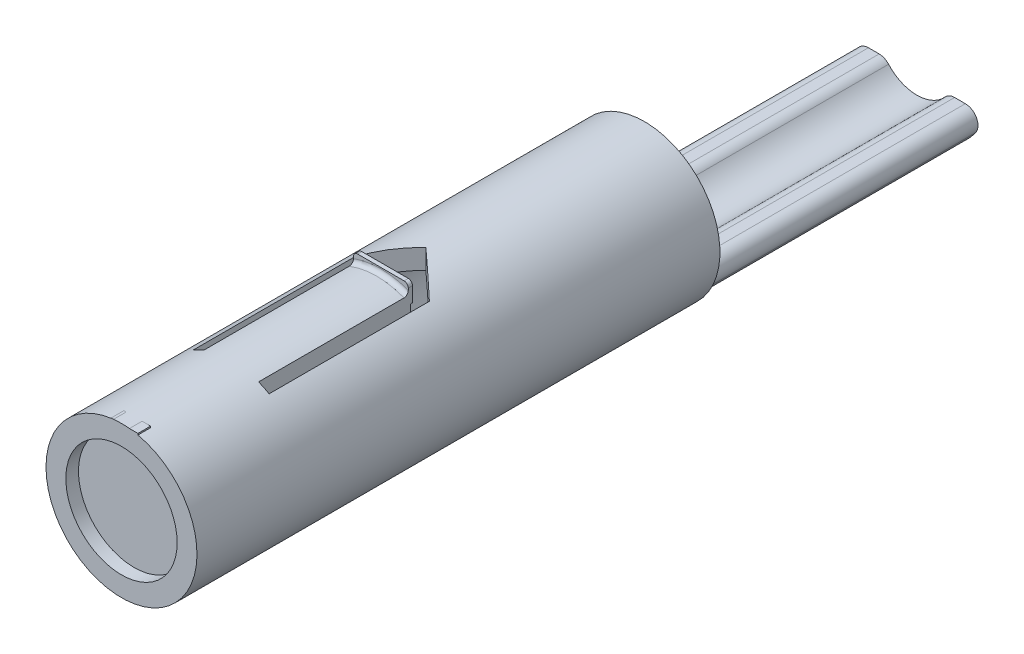
SolidWorks part; units mm, degrees
ref_plane "Front Plane" through (0, 0, 0) normal (0, 0, 1) x (1, 0, 0)
ref_plane "Top Plane" through (0, 0, 0) normal (0, 1, 0) x (1, 0, 0)
ref_plane "Right Plane" through (0, 0, 0) normal (1, 0, 0) x (0, 0, -1)
sketch "Sketch1" plane through (0, 0, 0) normal (0, 0, 1) x (1, 0, 0)
  circle A0 centre (0, 0) radius 8.95
  circle A1 centre (0, 0) radius 6.6
extrude "Boss-Extrude1" add sketch "Sketch1" along normal blind 62
sketch "Sketch2" plane through (0, 0, 62) normal (0, 0, 1) x (1, 0, 0)
  circle A0 centre (0, 0) radius 6.6
extrude "Boss-Extrude2" add sketch "Sketch2" against normal blind 7
sketch "Sketch4" plane through (0, 0, 62) normal (0, 0, 1) x (1, 0, 0)
  circle A0 centre (0, 0) radius 6.6
extrude "Cut-Extrude2" cut sketch "Sketch4" against normal blind 1.5
sketch "Sketch5" plane through (0, 0, 0) normal (0, 0, -1) x (-1, 0, 0)
  circle A0 centre (0, 0) radius 8.95
extrude "Boss-Extrude4" add sketch "Sketch5" against normal blind 10
sketch "Sketch6" plane through (0, 0, 0) normal (0, 0, -1) x (-1, 0, 0)
  circle A0 centre (0, 0) radius 9.0755
extrude "Boss-Extrude5" add sketch "Sketch6" along normal blind 32.3
sketch "Sketch7" plane through (0, 0, -32.3) normal (0, 0, -1) x (-1, 0, 0)
  line L1 (-5.8318, 9.3631) -> (5.9783, 9.3631)
  line L2 (-5.8318, 9.3631) -> (-5.8318, 2.7108)
  line L3 (-5.8318, 2.7108) -> (5.9783, 2.7108)
  line L4 (5.9783, 9.3631) -> (5.9783, 2.7108)
extrude "Cut-Extrude3" cut sketch "Sketch7" against normal blind 32.3
sketch "Sketch9" plane through (0, 0, -32.3) normal (0, 0, -1) x (-1, 0, 0)
  line L1 (-7.75, -9.08) -> (7.75, -9.08)
  line L2 (-7.75, -9.08) -> (-7.75, -0.98)
  line L3 (-7.75, -0.98) -> (7.75, -0.98)
  line L4 (7.75, -9.08) -> (7.75, -0.98)
  line L5 (-14.7241, -0.98) -> (14.7072, -0.98)
  line L6 (-14.7241, -0.98) -> (-14.7241, 9.3882)
  line L7 (-14.7241, 9.3882) -> (14.7072, 9.3882)
  line L8 (14.7072, -0.98) -> (14.7072, 9.3882)
  circle A0 centre (0, 0) radius 4.5
  arc A1 (-5.8318, 6.9537) -> (5.9783, 6.8282) centre (0, 0) ccw construction
  circle A2 centre (0, 0) radius 9.0755
  line M1 (-5.8318, 2.7108) -> (-5.8318, 6.9537)
  arc M2 (-5.8318, 6.9537) -> (5.9783, 6.8282) centre (0, 0) ccw
  line M3 (5.9783, 6.8282) -> (5.9783, 2.7108)
  line M4 (5.9783, 2.7108) -> (-5.8318, 2.7108)
  dimension "D1" = 9.08
  dimension "D5" = 9
  dimension "D2" = 8.1
  dimension "D3" = 7.75
  dimension "D4" = 15.5
extrude "Cut-Extrude4" cut sketch "Sketch9" against normal blind 32.3 contours L5 L2 M2 | A0 L5 L3 M4 M1 M2 | A0 L5 M4 | A0 M4 | L5 A0 | A0 L3 L5 M2 M3 M4 | L5 L4 M2 | L1 L4 L2 M2 region at (7.589, -6.9012, -32.3) region at (8.2315, -2.3544, -32.3) region at (-8.2315, -2.3544, -32.3) region at (6.695, 1.8863, -32.3) region at (-6.7152, 1.8118, -32.3) region at (0, 0.8102, -32.3) region at (0, -2.4494, -32.3) region at (0, 3.4402, -32.3)
fillet "Fillet5" radius 3 4 edges at (-4.392, -0.98, -16.15) (4.392, -0.98, -16.15) (-7.75, -0.98, -16.15) (7.75, -0.98, -16.15)
sketch "Sketch11" plane through (0, 0, 60.5) normal (0, 0, 1) x (1, 0, 0)
  line L1 (-1.2223, 8.9) -> (1.9499, 8.9)
  line L2 (-1.2223, 8.9) -> (-1.2223, 7.5322)
  line L3 (-1.2223, 7.5322) -> (1.9499, 7.5322)
  line L4 (1.9499, 8.9) -> (1.9499, 7.5322)
  circle A0 centre (0, 0) radius 8.95 construction
  dimension "D1" = 8.9
sketch "Sketch16" plane through (0, 0, -32.3) normal (0, 0, -1) x (-1, 0, 0)
  line L1 (-5.5534, -1.0896) -> (5.5566, -1.0896)
  line L2 (-5.5534, -1.0896) -> (-5.5534, -7.0896)
  line L3 (-5.5534, -7.0896) -> (5.5566, -7.0896)
  line L4 (5.5566, -1.0896) -> (5.5566, -7.0896)
  arc A0 (-3.8141, -2.388) -> (-7.2927, -2.388) centre (-5.5534, -7.0896) ccw
  arc A1 (3.8141, -2.388) -> (7.2908, -2.385) centre (5.5566, -7.0896) cw
  arc A2 (7.75, -3.98) -> (5.5534, -1.0896) centre (4.75, -3.98) ccw construction
  arc A3 (-5.5534, -1.0896) -> (-7.75, -3.98) centre (-4.75, -3.98) ccw construction
  arc M1 (7.75, -3.98) -> (5.5534, -1.0896) centre (4.75, -3.98) ccw
  arc M2 (5.5534, -1.0896) -> (3.8141, -2.388) centre (6.3569, -3.98) ccw
  arc M4 (-3.8141, -2.388) -> (-5.5534, -1.0896) centre (-6.3569, -3.98) ccw
  arc M5 (-5.5534, -1.0896) -> (-7.75, -3.98) centre (-4.75, -3.98) ccw
  dimension "D1" = 11.11
  dimension "D2" = 6
extrude "Cut-Extrude9" cut sketch "Sketch16" against normal blind 32.3 contours L2 M5 | L2 M4 | L4 M1 M2 | L4 M1 region at (4.905, -1.7713, -32.3) region at (6.2019, -1.7713, -32.3) region at (-4.9068, -1.7704, -32.3) region at (-6.2029, -1.7706, -32.3)
extrude "Boss-Extrude8" add sketch "Sketch11" along normal blind 2
sketch "Sketch13" plane through (0, 8.9, 0) normal (0, 1, 0) x (1, 0, 0)
  line L0 (-4.5, -30) -> (0, -25.9142)
  line L1 (-4.5, -30) -> (4.5, -30)
  line L2 (-4.5, -30) -> (-4.5, -49)
  line L3 (-4.5, -49) -> (4.5, -49)
  line L4 (4.5, -30) -> (4.5, -49)
  line L5 (-3.25, -49) -> (3.25, -49)
  line L6 (-3.25, -49) -> (-3.25, -31)
  line L7 (-3.25, -31) -> (3.25, -31)
  line L8 (3.25, -49) -> (3.25, -31)
  line L9 (0, -25.9142) -> (4.5, -30)
  dimension "D1" = 30
  dimension "D2" = 19
  dimension "D3" = 9
  dimension "D4" = 4.5
  dimension "D5" = 6.5
  dimension "D6" = 1.25
  dimension "D7" = 18
extrude "Cut-Extrude7" cut sketch "Sketch13" against normal blind 5 and the other way blind 5 contours L9 L0 L1 | L8 L3 L4 L1 L2 L6 L7 region at (0, 8.9, 28.6381) region at (0, 8.9, 30.2102)
sketch "Sketch14" plane through (0, 0, 62.5) normal (0, 0, 1) x (1, 0, 0)
  line L1 (-1.2223, 8.9) -> (1.9499, 8.9)
  line L2 (-1.2223, 8.9) -> (-1.2223, 7.5322)
  line L3 (-1.2223, 7.5322) -> (1.9499, 7.5322)
  line L4 (1.9499, 8.9) -> (1.9499, 7.5322)
extrude "Cut-Extrude8" cut sketch "Sketch14" against normal blind 0.5
sketch "Sketch15" plane through (0, 0, 0) normal (0, 0, -1) x (-1, 0, 0)
sketch "Sketch17" plane through (0, 0, 0) normal (0, 0, -1) x (-1, 0, 0)
  line L1 (-5, 1.8856) -> (5, 1.8856)
  line L2 (-5, 1.8856) -> (-5, -3.75)
  line L3 (-5, -3.75) -> (5, -3.75)
  line L4 (5, 1.8856) -> (5, -3.75)
  dimension "D1" = 5
  dimension "D2" = 10
  dimension "D3" = 3.75
extrude "Cut-Extrude11" cut sketch "Sketch17" along normal blind 33
sketch "Sketch18" plane through (0, 0, -32.3) normal (0, 0, -1) x (-1, 0, 0)
  line L0 (-2.4875, -3.75) -> (-5, -3.75)
  line L1 (-5, -3.75) -> (-5, -2.1072)
  line L2 (5, -2.1065) -> (5, -3.75)
  line L3 (5, -3.75) -> (2.5068, -3.7501)
  arc A0 (0, 0) -> (-2.4875, -3.75) centre (-2.507, -1.0371) ccw
  arc A1 (0, 0) -> (5, -2.1065) centre (2.5068, -1.0372) ccw
  line M2 (-5, -3.75) -> (-5, -2.1072)
  line M10 (5, -2.1065) -> (5, -3.75)
  line M11 (5, -3.75) -> (2.4875, -3.75)
extrude "Boss-Extrude9" add sketch "Sketch18" against normal blind 33 contours A0 L0 M2 | A1 M11 M10 region at (-4.4203, -3.3002, -32.3) region at (4.4204, -3.3003, -32.3)
sketch "Sketch20" plane through (0, 0, 31) normal (0, 0, -1) x (-1, 0, 0)
  line L1 (3.25, 8.3391) -> (-3.25, 8.3391)
  line L2 (3.25, 8.3391) -> (3.25, 9.5891)
  line L3 (3.25, 9.5891) -> (-3.25, 9.5891)
  line L4 (-3.25, 8.3391) -> (-3.25, 9.5891)
  dimension "D1" = 1.25
extrude "Boss-Extrude10" add sketch "Sketch20" along normal blind 0.25 and the other way blind 0.25
sketch "Sketch21" plane through (0, 0, 31) normal (0, 0, -1) x (-1, 0, 0)
  line L0 (3.25, 8.3391) -> (3.25, 5.7443) construction
  line L1 (-3.25, 8.3391) -> (3.25, 8.3391)
  line L2 (-3.25, 8.3391) -> (-3.25, 7.3391)
  line L3 (-3.25, 7.3391) -> (3.25, 7.3391)
  line L4 (3.25, 8.3391) -> (3.25, 7.3391)
  dimension "D1" = 1
extrude "Boss-Extrude11" add sketch "Sketch21" along normal blind 0.25 and the other way blind 0.25
fillet "Fillet6" radius 0.5 3 edges at (0, 8.95, 31.25) (3.25, 9.5891, 31) (-3.25, 9.5891, 31)
sketch "Sketch25" plane through (0, 0, -32.3) normal (0, 0, -1) x (-1, 0, 0)
  circle A0 centre (0, 0) radius 9.0755
extrude "Cut-Extrude18" cut sketch "Sketch25" against normal blind 32.3
sketch "Sketch26" plane through (0, 0, 0) normal (0, 0, -1) x (-1, 0, 0)
  line L1 (-8.5, 0) -> (9.5, 0)
  line L2 (-8.5, 0) -> (-8.5, -2.5)
  line L3 (-8.5, -2.5) -> (9.5, -2.5)
  line L4 (9.5, 0) -> (9.5, -2.5)
  circle A0 centre (0, 0) radius 8.5
  circle A1 centre (0, 0) radius 4.5
  dimension "D1" = 2.5
  dimension "D2" = 9
  dimension "D3" = 17
  dimension "D4" = 18
extrude "Boss-Extrude13" add sketch "Sketch26" along normal blind 32.3 contours A1 L3 A0 region at (0, -5.2802, 0)
fillet "Fillet8" radius 1.5 4 edges at (-8.124, -2.5, -16.15) (-3.7417, -2.5, -16.15) (3.7417, -2.5, -16.15) (8.124, -2.5, -16.15)
